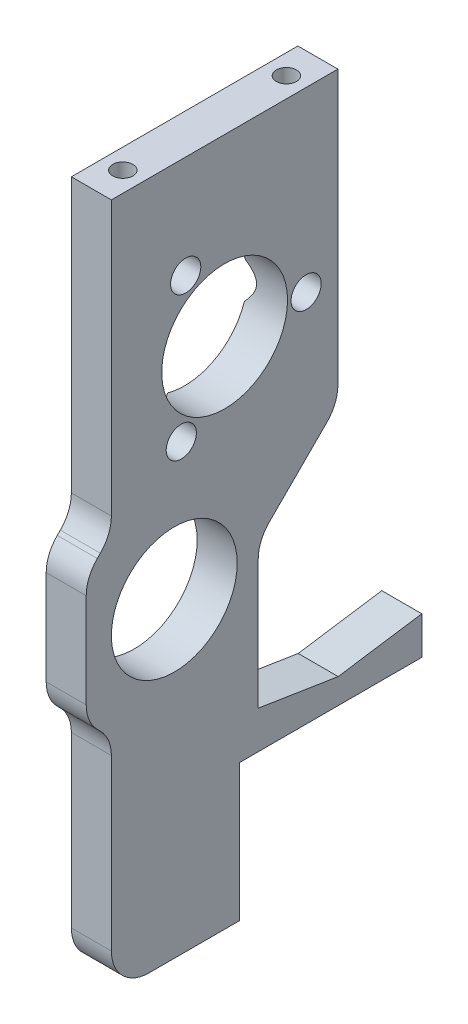
SolidWorks part; units mm, degrees
ref_plane "Front Plane" through (0, 0, 0) normal (0, 0, 1) x (1, 0, 0)
ref_plane "Top Plane" through (0, 0, 0) normal (0, 1, 0) x (1, 0, 0)
ref_plane "Right Plane" through (0, 0, 0) normal (1, 0, 0) x (0, 0, -1)
sketch "Sketch2" plane through (0, 0, 0) normal (1, 0, 0) x (0, 0, -1)
  line L0 (-7.3996, 19.4136) -> (10.6004, 19.4136)
  line L1 (10.6004, 19.4136) -> (10.6004, -3.5864)
  line L2 (2.7704, -35.2864) -> (-7.3996, -35.2864)
  line L3 (-9.3996, -15.5864) -> (-9.3996, -5.5864)
  line L4 (-21.5473, -39.2864) -> (35.9179, -39.2864) construction
  line L14 (-7.3996, -3.5864) -> (-7.3996, 19.4136)
  line L16 (-7.3996, -17.5864) -> (-7.3996, -35.2864)
  line L19 (2.7704, -35.2864) -> (2.7704, -24.4064)
  line L20 (2.7704, -24.4064) -> (17.2704, -24.4064)
  line L25 (-9.3996, -5.5864) -> (-7.3996, -3.5864)
  line L26 (-9.3996, -15.5864) -> (-7.3996, -17.5864)
  line L28 (-2.3996, -5.5864) -> (-9.3996, -5.5864) construction
  line L29 (-2.3996, -15.5864) -> (-9.3996, -15.5864) construction
  line L30 (10.6004, -3.5864) -> (4.2704, -9.9164)
  line L31 (4.2704, -9.9164) -> (4.2704, -21.4064)
  line L38 (4.2704, -21.4064) -> (10.6253, -22.4064)
  line L39 (10.6253, -22.4064) -> (17.2704, -21.4064)
  line L40 (17.2704, -21.4064) -> (17.2704, -24.4064)
  line L42 (-3.3996, 10.5244) -> (6.6004, 10.5244) construction
  line L43 (-3.3996, 10.5244) -> (-3.3996, 0.5244) construction
  line L44 (-3.3996, 0.5244) -> (6.6004, 0.5244) construction
  line L45 (6.6004, 10.5244) -> (6.6004, 0.5244) construction
  circle A1 centre (-2.3996, -10.5864) radius 5
  circle A2 centre (1.6004, 5.5244) radius 8 construction
  circle A3 centre (1.6004, 5.5244) radius 5
  dimension "D1" = 28.7
  dimension "D2" = 2
  dimension "D4" = 18
  dimension "D6" = 16
  dimension "D7" = 10
  dimension "D3" = 10
  dimension "D10" = 2
  dimension "D9" = 2
  dimension "D5" = 16.6
  dimension "D8" = 9
  dimension "D11" = 1
  dimension "D12" = 10.88
  dimension "D13" = 4
  dimension "D14" = 13
  dimension "D15" = 1.5
  dimension "D16" = 10.17
  dimension "D17" = 23
extrude "Boss-Extrude1" add sketch "Sketch2" against normal blind 3.18 contours L0 L1 L30 L31 L38 L39 L40 L20 L19 L2 L16 L26 L3 L25 L14
extrude "Cut-Extrude2" cut sketch "Sketch2<4>" against normal blind 3.18 flip side to cut
sketch "Sketch2<4>" plane through (0, 0, 0) normal (1, 0, 0) x (0, 0, -1) same geometry as "Sketch2"
fillet "Fillet6" radius 3 7 edges at (-1.59, -17.5864, 7.3996) (-1.59, -15.5864, 9.3996) (-1.59, -5.5864, 9.3996) (-1.59, -3.5864, 7.3996) (-1.59, -35.2864, 7.3996) (-1.59, -3.5864, -10.6004) (-1.59, -9.9164, -4.2704)
hole_wizard "M2x0.4 Tapped Hole1" positions "Sketch5" profile "Sketch6" tap size "M2x0.4" standard "ANSI Metric"
sketch "Sketch5" plane through (0, 19.4136, 0) normal (0, 1, 0) x (1, 0, 0)
  line L0 (-3.18, 10.6004) -> (0, 10.6004) construction
  line L1 (-3.18, -7.3996) -> (0, -7.3996) construction
  line L2 (0, -7.3996) -> (0, 10.6004) construction
  point P0 (-1.59, 8.1004)
  point P2 (-1.59, -4.8996)
  point P13 (-1.59, 8.1004)
  dimension "D1" = 2.5
  dimension "D2" = 2.5
  dimension "D3" = 1.59
sketch "Sketch6" plane through (-1.59, 19.4136, -8.1004) normal (1, 0, 0) x (0, 0, 1)
  line L0 (0, 0) -> (0, 6)
  line L1 (0, 6) -> (0.8, 5.5193)
  line L2 (0.8, 5.5193) -> (0.8, 0)
  line L5 (0.8, 0) -> (0, 0)
  line L10 (0, 6) -> (-0.8, 5.5193) construction
  line L11 (0, -6.35) -> (0, 107.95) construction
  dimension "Tap Drill Dia." = 1.6
  dimension "Tap Drill Depth" = 6
  dimension "Drill Angle" = 118
mirror "Mirror1" [suppressed] of bodies 104
delete or keep bodies "Body-Delete/Keep 1" [suppressed] type delete bodies bodies 104
sketch "Sketch7" plane through (0, 0, -3.18) normal (1, 0, 0) x (0, 0, -1)
  circle A0 centre (-4.6747, 11.2539) radius 1
  circle A1 centre (4.8965, 5.3257) radius 1
  circle A2 centre (-5.023, 0.001) radius 1
extrude "Cut-Extrude3" cut sketch "Sketch7" against normal up to next
hole_wizard "CSK for M2 Flat Head Machine Screw1" positions "Sketch8" profile "Sketch9" countersink size "M2" standard "ANSI Metric" end condition up to next
sketch "Sketch8" plane through (-3.18, 0, 0) normal (-1, 0, 0) x (0, 0, 1)
  point P0 (-8.0765, 5.3257)
  point P3 (1.4947, 11.2539)
  point P6 (1.843, 0.001)
sketch "Sketch9" plane through (-3.18, 5.3257, -8.0765) normal (0, 1, 0) x (0, 0, 1)
  line L0 (0, 0) -> (0, 3.18)
  line L1 (0, 3.18) -> (1.2, 3.18)
  line L2 (1.2, 3.18) -> (1.2, 1)
  line L3 (1.2, 1) -> (2.2, 0)
  line L5 (2.2, 0) -> (0, 0)
  line L6 (-1.2, 1) -> (-2.2, 0) construction
  line L11 (0, -6.35) -> (0, 107.95) construction
  dimension "Thru Hole Dia." = 2.4
  dimension "Thru Hole Depth" = 3.18
  dimension "Near C'Sink Dia." = 4.4
  dimension "Near C'Sink Angle" = 90
equation "\"RollerToBaseplate\"= 28.7mm"
equation "\"SteelShaftDia\"= 10mm"
equation "\"DribblerMotorDia\"= 16mm"
equation "\"DribblerHeight\"= 50mm"
